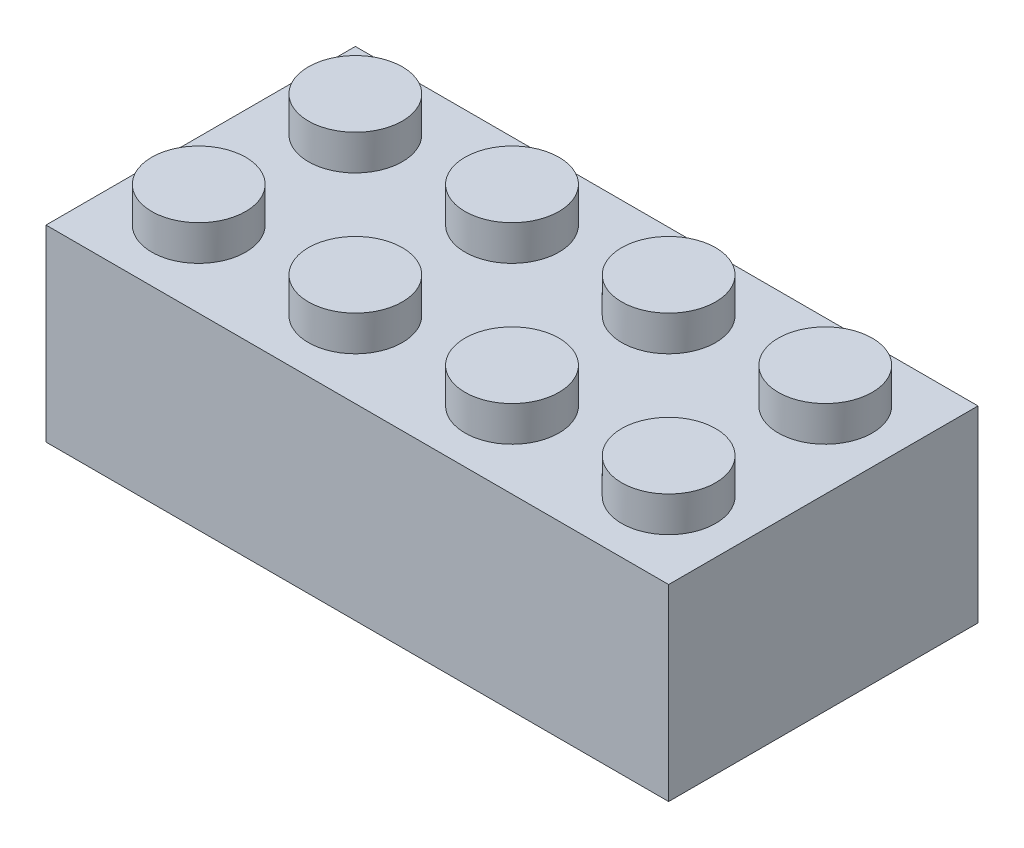
SolidWorks part; units mm, degrees
ref_plane "Front Plane" through (0, 0, 0) normal (0, 0, 1) x (1, 0, 0)
ref_plane "Top Plane" through (0, 0, 0) normal (0, 1, 0) x (1, 0, 0)
ref_plane "Right Plane" through (0, 0, 0) normal (1, 0, 0) x (0, 0, -1)
sketch "Sketch1" plane through (0, 0, 0) normal (0, 1, 0) x (1, 0, 0)
  line L1 (0, 0) -> (31.8, 0)
  line L2 (0, 0) -> (0, 15.8)
  line L3 (0, 15.8) -> (31.8, 15.8)
  line L4 (31.8, 0) -> (31.8, 15.8)
  dimension "D1" = 31.8
  dimension "D2" = 15.8
extrude "Boss-Extrude1" add sketch "Sketch1" along normal blind 9.6
shell "Shell1" thickness 1.2 removed face at (15.9, 0, -7.9)
sketch "Sketch2" plane through (0, 9.6, 0) normal (0, 1, 0) x (1, 0, 0)
  line L0 (31.8, 0) -> (31.8, 15.8) construction
  line L1 (31.8, 15.8) -> (0, 15.8) construction
  circle A0 centre (27.9, 11.9) radius 2.4
  circle A1 centre (19.9, 11.9) radius 2.4
  circle A2 centre (11.9, 11.9) radius 2.4
  circle A3 centre (3.9, 11.9) radius 2.4
  circle A4 centre (19.9, 3.9) radius 2.4
  circle A5 centre (11.9, 3.9) radius 2.4
  circle A6 centre (3.9, 3.9) radius 2.4
  circle A7 centre (27.9, 3.9) radius 2.4
  dimension "D1" = 4.8
  dimension "D2" = 3.9
  dimension "D3" = 3.9
  dimension "D4" = 4
  dimension "D5" = 2
extrude "Boss-Extrude2" add sketch "Sketch2" along normal blind 1.8
sketch "Sketch3" plane through (0, 8.4, 0) normal (0, -1, 0) x (-1, 0, 0)
  line L0 (0, 15.8) -> (0, 0) construction
  line L5 (0, 0) -> (-31.8, 0) construction
  circle A0 centre (-3.9, 3.9) radius 1.4
  circle A1 centre (-11.9, 3.9) radius 1.4
  circle A2 centre (-19.9, 3.9) radius 1.4
  circle A3 centre (-27.9, 3.9) radius 1.4
  circle A4 centre (-11.9, 11.9) radius 1.4
  circle A5 centre (-19.9, 11.9) radius 1.4
  circle A6 centre (-27.9, 11.9) radius 1.4
  circle A7 centre (-3.9, 11.9) radius 1.4
  dimension "D1" = 2.8
  dimension "D2" = 3.9
  dimension "D3" = 3.9
  dimension "D4" = 4
  dimension "D5" = 2
extrude "Cut-Extrude1" cut sketch "Sketch3" against normal blind 1.7
sketch "Sketch5" plane through (0, 8.4, 0) normal (0, -1, 0) x (1, 0, 0)
  line L0 (1.2, -8.1839) -> (30.6, -8.1839) construction
  line L1 (1.2, -14.6) -> (1.2, -1.2) construction
  line L2 (30.6, -1.2) -> (30.6, -14.6) construction
  line L3 (30.6, -8.1839) -> (15.9, -8.1839)
  line L4 (15.9, -8.1839) -> (15.9, -14.6) construction
  line L5 (30.6, -14.6) -> (1.2, -14.6) construction
  line L6 (1.2, -1.2) -> (30.6, -1.2) construction
  line L7 (16.3, -14.6) -> (15.5, -14.6)
  line L8 (16.3, -14.6) -> (16.3, -1.2)
  line L9 (16.3, -1.2) -> (15.5, -1.2)
  line L10 (15.5, -14.6) -> (15.5, -1.2)
  dimension "D1" = 0.8
  dimension "D2" = 0.4
extrude "Boss-Extrude3" add sketch "Sketch5" along normal blind 6.3
sketch "Sketch7" plane through (0, 0, -15.8) normal (0, 0, -1) x (-1, 0, 0)
  line L0 (-31.8, 2.6129) -> (0, 2.6129) construction
  line L1 (-31.8, 9.6) -> (-31.8, 0) construction
  line L2 (0, 9.6) -> (0, 0) construction
  text T0 "RUSSELL"
extrude "Cut-Extrude2" cut sketch "Sketch7" against normal blind 1.21
sketch "Sketch9" plane through (0, 0, -15.8) normal (0, 0, -1) x (-1, 0, 0)
  line L5 (-24.4705, 6.1129) -> (-23.7701, 6.1129) construction
  line L6 (-24.1564, 4.2283) -> (-23.9013, 4.2283)
  line L7 (-24.1564, 4.2283) -> (-24.1564, 6.1129)
  line L8 (-24.1564, 6.1129) -> (-23.9013, 6.1129)
  line L9 (-23.9013, 4.2283) -> (-23.9013, 6.1129)
extrude "Boss-Extrude5" add sketch "Sketch9" against normal blind 1.2
sketch "Sketch10" plane through (0, 8.4, 0) normal (0, -1, 0) x (1, 0, 0)
  line L0 (31.8, 0) -> (31.8, -15.8) construction
  line L1 (31.8, -15.8) -> (0, -15.8) construction
  circle A0 centre (23.9, -7.9) radius 3.255
  circle A1 centre (15.9, -7.9) radius 3.255
  circle A2 centre (7.9, -7.9) radius 3.255
  dimension "D1" = 6.51
  dimension "D2" = 7.9
  dimension "D3" = 7.9
  dimension "D4" = 3
extrude "Boss-Extrude6" add sketch "Sketch10" along normal up to vertex (8.4 mm away) up to point (30.6, 0, -1.2)
sketch "Sketch14" plane through (0, 0, 0) normal (0, -1, 0) x (1, 0, 0)
  circle A0 centre (7.9, -7.9) radius 3.255
  circle A1 centre (7.9, -7.9) radius 2.4
  circle A2 centre (15.9, -7.9) radius 2.4 construction
  circle A3 centre (23.9, -7.9) radius 2.4 construction
  dimension "D1" = 6.51
  dimension "D2" = 4.8
  dimension "D3" = 3
extrude "Cut-Extrude5" cut sketch "Sketch14" against normal up to surface (8.4 mm away) contours A1 up to face at (7.9, 8.4, -11.155)
sketch "Sketch17" plane through (0, 0, 0) normal (0, -1, 0) x (1, 0, 0)
  circle A0 centre (15.9, -7.9) radius 3.255
  circle A1 centre (22.9021, -10.9723) radius 0.0247
  circle A2 centre (15.9, -7.9) radius 2.4
  dimension "D1" = 6.51
  dimension "D2" = 4.8
extrude "Cut-Extrude6" cut sketch "Sketch17" against normal up to surface (8.4 mm away) contours A2 up to face at (7.9, 8.4, -11.155)
sketch "Sketch18" plane through (0, 0, 0) normal (0, -1, 0) x (-1, 0, 0)
  circle A0 centre (-20.7371, 7.1851) radius 0.0124
  circle A1 centre (-23.9, 7.9) radius 3.255 construction
  circle A3 centre (-23.9, 7.9) radius 2.4
  point P4 (0, 0)
  dimension "D1" = 0
  dimension "D2" = 4.8
extrude "Cut-Extrude7" cut sketch "Sketch18" against normal up to surface (8.4 mm away) contours A3 up to face at (23.9, 8.4, -11.155)
sketch "Sketch19" plane through (0, 0, -1.2) normal (0, 0, -1) x (-1, 0, 0)
  line L0 (-16.3, 8.4) -> (-30.6, 8.4) construction
  line L1 (-1.2, 0) -> (-30.6, 0) construction
  line L2 (-28.2, 8.4) -> (-27.5927, 8.4)
  line L3 (-28.2, 8.4) -> (-28.2, 0)
  line L4 (-28.2, 0) -> (-27.5927, 0)
  line L5 (-27.5927, 8.4) -> (-27.5927, 0)
  line L6 (-20.2, 8.4) -> (-20.2, 0)
  line L7 (-20.2, 8.4) -> (-19.5927, 8.4)
  line L8 (-19.5927, 8.4) -> (-19.5927, 0)
  line L9 (-20.2, 0) -> (-19.5927, 0)
  line L10 (-12.2, 8.4) -> (-12.2, 0)
  line L11 (-12.2, 8.4) -> (-11.5927, 8.4)
  line L12 (-11.5927, 8.4) -> (-11.5927, 0)
  line L13 (-12.2, 0) -> (-11.5927, 0)
  line L14 (-4.2, 8.4) -> (-4.2, 0)
  line L15 (-4.2, 8.4) -> (-3.5927, 8.4)
  line L16 (-3.5927, 8.4) -> (-3.5927, 0)
  line L17 (-4.2, 0) -> (-3.5927, 0)
  line L18 (-30.6, 8.4) -> (-30.6, 0) construction
  dimension "D1" = 0.6073
  dimension "D3" = 2.4
  dimension "D2" = 4
extrude "Boss-Extrude7" add sketch "Sketch19" along normal blind 0.2
sketch "Sketch21" plane through (0, 0, -14.6) normal (0, 0, 1) x (1, 0, 0)
  line L0 (15.5, 8.4) -> (1.2, 8.4) construction
  line L1 (3.6202, 8.4) -> (4.2202, 8.4)
  line L2 (3.6202, 8.4) -> (3.6202, 0)
  line L3 (3.6202, 0) -> (4.2202, 0)
  line L4 (4.2202, 8.4) -> (4.2202, 0)
  line L5 (30.6, 0) -> (1.2, 0) construction
  line L6 (11.6202, 8.4) -> (11.6202, 0)
  line L7 (11.6202, 8.4) -> (12.2202, 8.4)
  line L8 (12.2202, 8.4) -> (12.2202, 0)
  line L9 (11.6202, 0) -> (12.2202, 0)
  line L10 (19.6202, 8.4) -> (19.6202, 0)
  line L11 (19.6202, 8.4) -> (20.2202, 8.4)
  line L12 (20.2202, 8.4) -> (20.2202, 0)
  line L13 (19.6202, 0) -> (20.2202, 0)
  line L14 (27.6202, 8.4) -> (27.6202, 0)
  line L15 (27.6202, 8.4) -> (28.2202, 8.4)
  line L16 (28.2202, 8.4) -> (28.2202, 0)
  line L17 (27.6202, 0) -> (28.2202, 0)
  line L18 (1.2, 8.4) -> (1.2, 0) construction
  dimension "D1" = 0.6
  dimension "D3" = 2.4
  dimension "D2" = 4
extrude "Boss-Extrude8" add sketch "Sketch21" along normal blind 0.2
chamfer "Chamfer1" distance 0.2 angle 45 1 edges at (3.9202, 0, -14.4)
chamfer "Chamfer2" distance 0.2 angle 45 1 edges at (11.9202, 0, -14.4)
chamfer "Chamfer3" distance 0.2 angle 45 1 edges at (19.9202, 0, -14.4)
chamfer "Chamfer4" distance 0.2 angle 45 1 edges at (27.9202, 0, -14.4)
chamfer "Chamfer5" distance 0.2 angle 45 1 edges at (3.8964, 0, -1.4)
chamfer "Chamfer6" distance 0.2 angle 45 1 edges at (11.8964, 0, -1.4)
chamfer "Chamfer7" distance 0.2 angle 45 1 edges at (19.8964, 0, -1.4)
chamfer "Chamfer8" distance 0.2 angle 45 1 edges at (27.8964, 0, -1.4)
sketch "Sketch22" plane through (1.2, 0, 0) normal (1, 0, 0) x (0, 0, -1)
  line L0 (14.6, 8.4) -> (1.2, 8.4) construction
  line L1 (3.6, 8.4) -> (4.2, 8.4)
  line L2 (3.6, 8.4) -> (3.6, 0)
  line L3 (3.6, 0) -> (4.2, 0)
  line L4 (4.2, 8.4) -> (4.2, 0)
  line L5 (14.6, 0) -> (1.2, 0) construction
  line L6 (1.2, 8.4) -> (1.2, 0) construction
  line L7 (11.6, 8.4) -> (11.6, 0)
  line L8 (11.6, 8.4) -> (12.2, 8.4)
  line L9 (12.2, 8.4) -> (12.2, 0)
  line L10 (11.6, 0) -> (12.2, 0)
  dimension "D1" = 0.6
  dimension "D2" = 2.4
  dimension "D3" = 2
extrude "Boss-Extrude9" add sketch "Sketch22" along normal blind 0.2
chamfer "Chamfer9" distance 0.2 angle 45 1 edges at (1.4, 0, -3.9)
chamfer "Chamfer10" distance 0.2 angle 45 1 edges at (1.4, 0, -11.9)
sketch "Sketch23" plane through (30.6, 0, 0) normal (-1, 0, 0) x (0, 0, 1)
  line L0 (-1.2, 8.4) -> (-14.6, 8.4) construction
  line L1 (-12.2, 8.4) -> (-11.6, 8.4)
  line L2 (-12.2, 8.4) -> (-12.2, 0)
  line L3 (-12.2, 0) -> (-11.6, 0)
  line L4 (-11.6, 8.4) -> (-11.6, 0)
  line L5 (-1.2, 0) -> (-14.6, 0) construction
  line L6 (-14.6, 8.4) -> (-14.6, 0) construction
  line L7 (-4.2, 8.4) -> (-4.2, 0)
  line L8 (-4.2, 8.4) -> (-3.6, 8.4)
  line L9 (-3.6, 8.4) -> (-3.6, 0)
  line L10 (-4.2, 0) -> (-3.6, 0)
  dimension "D1" = 0.6
  dimension "D2" = 2.4
  dimension "D3" = 2
extrude "Boss-Extrude10" add sketch "Sketch23" along normal blind 0.2
chamfer "Chamfer11" distance 0.2 angle 45 1 edges at (30.4, 0, -11.9)
chamfer "Chamfer12" distance 0.2 angle 45 1 edges at (30.4, 0, -3.9)
